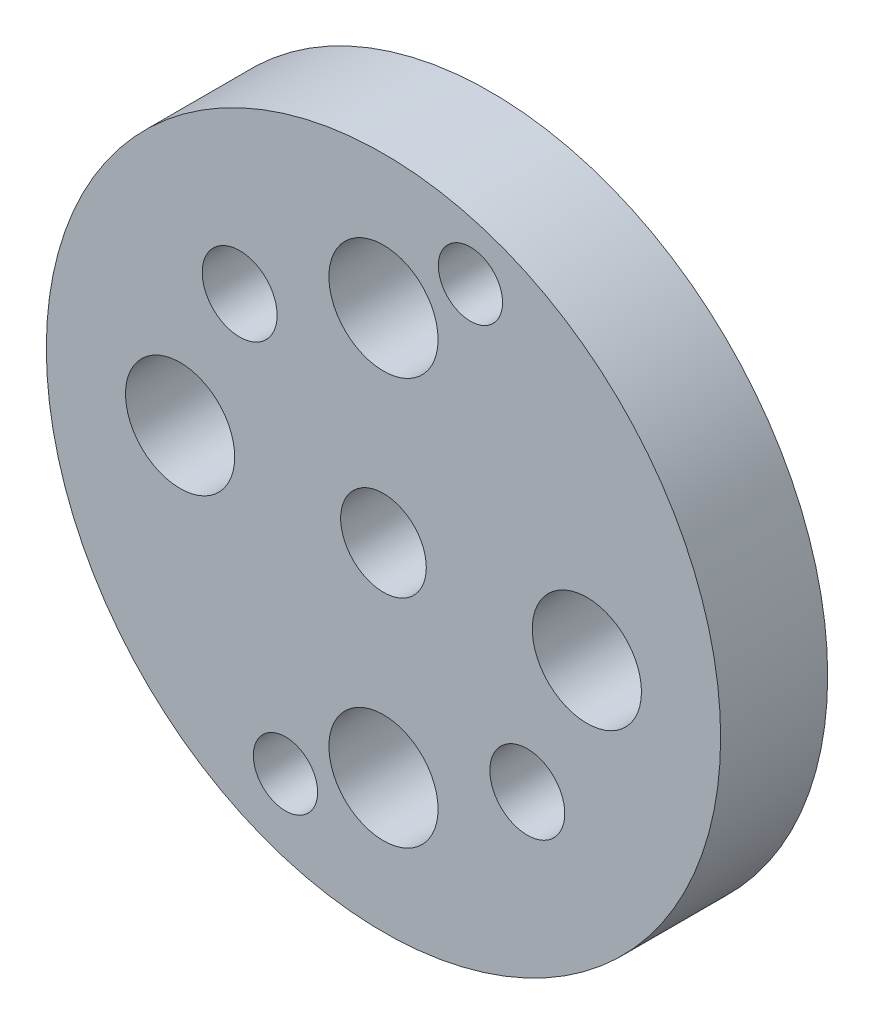
SolidWorks part; units mm, degrees
ref_plane "Front Plane" through (0, 0, 0) normal (0, 0, 1) x (1, 0, 0)
ref_plane "Top Plane" through (0, 0, 0) normal (0, 1, 0) x (1, 0, 0)
ref_plane "Right Plane" through (0, 0, 0) normal (1, 0, 0) x (0, 0, -1)
sketch "Sketch1" plane through (0, 0, 0) normal (0, 0, 1) x (1, 0, 0)
  line L0 (0, 0) -> (-19, 0) construction
  line L1 (0, 0) -> (0, 19) construction
  line L2 (0, 0) -> (13.4335, 13.4365) construction
  line L3 (-13.4365, 13.4335) -> (0, 0) construction
  circle A0 centre (0, 0) radius 31.5
  circle A1 centre (0, 0) radius 4
  circle A2 centre (0, 0) radius 19
  circle A3 centre (-19, 0) radius 5.1
  circle A4 centre (-19, 0) radius 3.5
  circle A5 centre (0, 19) radius 5.1
  circle A6 centre (0, 19) radius 3.5
  circle A7 centre (-13.4365, 13.4335) radius 3.5
  circle A8 centre (19, 0) radius 5.1
  circle A9 centre (19, 0) radius 3.5
  circle A10 centre (13.4365, -13.4335) radius 3.5
  circle A11 centre (0, -19) radius 3.5
  circle A12 centre (0, -19) radius 5.1
  circle A13 centre (8.1247, 25) radius 3
  circle A14 centre (-9.1563, -23.2629) radius 3
  circle A15 centre (8.1247, 25) radius 2.5
  circle A16 centre (-9.1563, -23.2629) radius 2.5
  circle A17 centre (13.4365, -13.4335) radius 3
  circle A18 centre (-13.4365, 13.4335) radius 3
  dimension "D1" = 63
  dimension "D2" = 8
  dimension "D3" = 10.2
  dimension "D4" = 38
  dimension "D5" = 7
  dimension "D6" = 10.2
  dimension "D7" = 7
  dimension "D8" = 7
  dimension "D12" = 6
  dimension "D15" = 6
  dimension "D18" = 5
  dimension "D19" = 5
  dimension "D20" = 6
  dimension "D21" = 6
  dimension "D9" = 14.54
  dimension "D10" = 14.5439
  dimension "D11" = 14.54
  dimension "D13" = 25
  dimension "D14" = 10.1
  dimension "D16" = 10.1
  dimension "D17" = 25
extrude "Boss-Extrude1" add sketch "Sketch1" along normal blind 10 contours A0 A14 A13 A2 A12 A3 A7 A5 A8 A10 | A2 A12 A10 A8 A5 A7 A3 A1 region at (-30.609, 0, 0) region at (13.382, 0, 0)
extrude "Boss-Extrude2" add sketch "Sketch1<3>" along normal blind 2 contours A4 A2 A3 | A4 A2 A3 | A18 A2 A7 | A18 A2 A7 | A6 A2 A5 | A6 A2 A5 | A13 A15 | A2 A9 A8 | A2 A9 A8 | A17 A2 A10 | A17 A2 A10 | A12 A2 A11 | A12 A2 A11 | A14 A16 region at (15.3882, 0, 0) region at (18.6275, 4.2997, 0) region at (0, 14.0118, 0) region at (4.2997, 18.6275, 0) region at (16.5256, -11.9835, 0) region at (15.4631, -10.9003, 0) region at (-10.221, 14.595, 0) region at (-11.001, 15.5985, 0) region at (4.9715, -18.6649, 0) region at (4.2482, -18.4043, 0) region at (-15.2436, 3.282, 0) region at (-18.6275, 4.2997, 0) region at (5.2095, 25, 0) region at (-12.0715, -23.2629, 0)
sketch "Sketch1<3>" plane through (0, 0, 0) normal (0, 0, 1) x (1, 0, 0) same geometry as "Sketch1"
